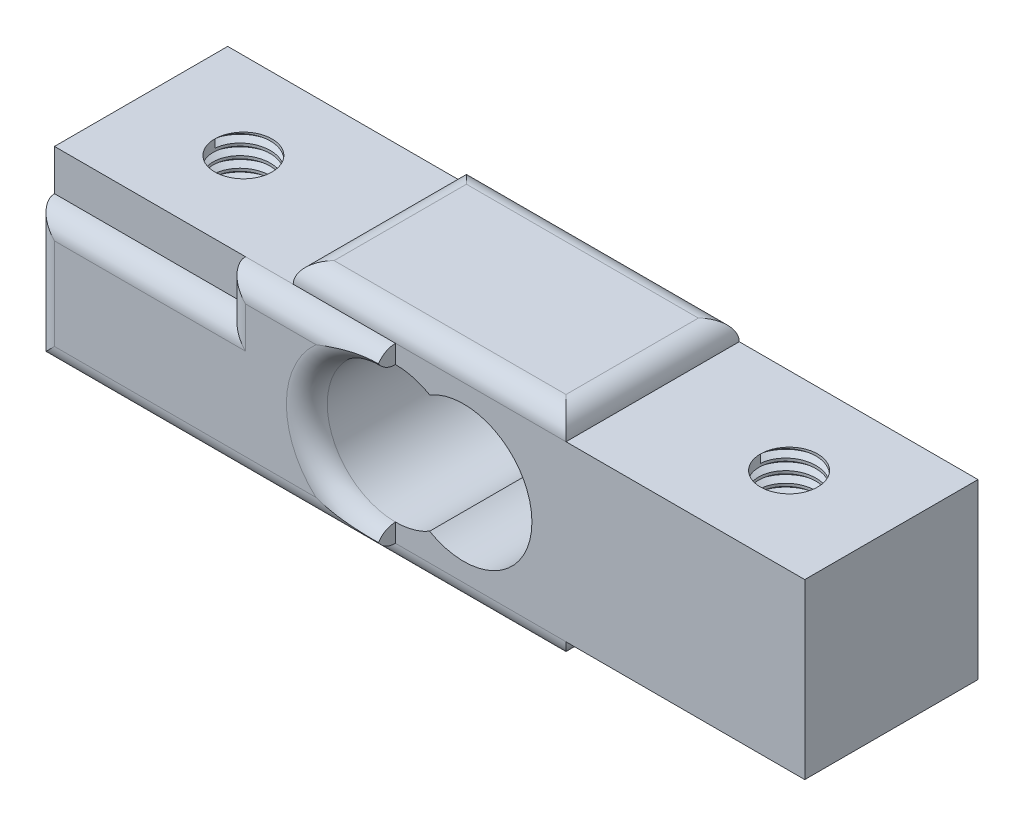
SolidWorks part; units mm, degrees
ref_plane "Front Plane" through (0, 0, 0) normal (0, 0, 1) x (1, 0, 0)
ref_plane "Top Plane" through (0, 0, 0) normal (0, 1, 0) x (1, 0, 0)
ref_plane "Right Plane" through (0, 0, 0) normal (1, 0, 0) x (0, 0, -1)
sketch "Sketch2" plane through (0, 0, 0) normal (0, 0, 1) x (1, 0, 0)
  line L1 (-27.5, -6.35) -> (27.5, -6.35)
  line L2 (-27.5, -6.35) -> (-27.5, 6.35)
  line L3 (-27.5, 6.35) -> (27.5, 6.35)
  line L4 (27.5, -6.35) -> (27.5, 6.35)
  line L5 (-27.5, -6.35) -> (27.5, 6.35) construction
  line L6 (-27.5, 6.35) -> (27.5, -6.35) construction
  point P0 (0, 0)
  dimension "D1" = 55
  dimension "D2" = 12.7
extrude "Boss-Extrude1" add sketch "Sketch2" along normal blind 12.7
sketch "Sketch3" plane through (0, 6.35, 0) normal (0, 1, 0) x (1, 0, 0)
  line L0 (-27.5, -6.35) -> (-20, -6.35) construction
  line L1 (-27.5, -12.7) -> (-27.5, 0) construction
  line L2 (27.5, -6.35) -> (20, -6.35) construction
  line L3 (27.5, -12.7) -> (27.5, 0) construction
  circle A0 centre (-20, -6.35) radius 2.5
  circle A1 centre (20, -6.35) radius 2.5
  dimension "D1" = 5
  dimension "D2" = 5
  dimension "D3" = 7.5
  dimension "D4" = 7.5
  dimension "D5" = 40
sketch "Sketch4" plane through (0, 0, 12.7) normal (0, 0, 1) x (1, 0, 0)
  line L0 (0, 0) -> (-2.5, 0) construction
  line L1 (0, 0) -> (2.5, 0) construction
  circle A0 centre (-2.5, 0) radius 5
  circle A1 centre (2.5, 0) radius 5
  dimension "D3" = 10
  dimension "D4" = 10
  dimension "D1" = 2.5
  dimension "D2" = 2.5
extrude "Cut-Extrude2" cut sketch "Sketch4" against normal blind 12.7 contours A0 A1 | A0 A1 | A1 A0 region at (0, 0, 12.7) region at (4.1051, 0, 12.7) region at (-4.1051, 0, 12.7)
sketch "Sketch5" plane through (0, 6.35, 0) normal (0, 1, 0) x (1, 0, 0)
  line L2 (-10, -6.35) -> (-10, -12.7) construction
  line L3 (27.5, -12.7) -> (-27.5, -12.7) construction
  line L4 (-10, -12.7) -> (10, -12.7) construction
  line L5 (10, -12.7) -> (10, 0) construction
  line L6 (27.5, 0) -> (-27.5, 0) construction
  line L7 (10, 0) -> (-10, 0) construction
  line L8 (-10, 0) -> (-10, -6.35) construction
  line L9 (10, -6.35) -> (27.5, -6.35) construction
  line L10 (-10, -12.7) -> (10, -12.7)
  line L11 (-10, -12.7) -> (-10, 0)
  line L12 (-10, 0) -> (10, 0)
  line L13 (10, -12.7) -> (10, 0)
  line L14 (-10, -6.35) -> (-27.5, -6.35) construction
  dimension "D1" = 20
extrude "Boss-Extrude2" add sketch "Sketch5" along normal blind 1.5
hole_wizard "Tap Drill for M5x0.8 Tap1" positions "3DSketch1" profile "Sketch8" hole size "M5x0.8" standard "ANSI Metric" end condition through all
sketch3d "3DSketch1"
  point P0 (-20, 6.35, 6.35)
  point P3 (20, 6.35, 6.35)
sketch "Sketch8" plane through (-20, 6.35, 6.35) normal (1, 0, 0) x (0, 0, 1)
  line L0 (0, 0) -> (0, 12.7)
  line L1 (0, 12.7) -> (2.1, 12.7)
  line L2 (2.1, 12.7) -> (2.1, 0)
  line L5 (2.1, 0) -> (0, 0)
  line L11 (0, -6.35) -> (0, 107.95) construction
  dimension "Thru Hole Dia." = 4.2
  dimension "Thru Hole Depth" = 12.7
fillet "Fillet1" radius 1.5 4 edges at (0, 7.85, 0) (10, 7.85, 6.35) (-10, 7.85, 6.35) (0, 7.85, 12.7)
sketch "Sketch6" plane through (0, -6.35, 0) normal (0, -1, 0) x (-1, 0, 0)
  line L0 (10, -6.35) -> (27.5, -6.35) construction
  line L1 (27.5, -12.7) -> (27.5, 0) construction
  line L2 (10, -6.35) -> (10, 0) construction
  line L3 (27.5, 0) -> (-27.5, 0) construction
  line L4 (10, 0) -> (-10, 0) construction
  line L5 (-10, 0) -> (-10, -12.7) construction
  line L6 (-10, -12.7) -> (10, -12.7) construction
  line L7 (27.5, -12.7) -> (-27.5, -12.7) construction
  line L8 (10, -12.7) -> (10, -6.35) construction
  line L10 (10, 0) -> (-10, 0)
  line L11 (10, 0) -> (10, -12.7)
  line L12 (10, -12.7) -> (-10, -12.7)
  line L13 (-10, 0) -> (-10, -12.7)
  dimension "D1" = 20
extrude "Boss-Extrude3" add sketch "Sketch6" along normal blind 1.5
fillet "Fillet2" radius 1.5 4 edges at (0, -7.85, 12.7) (10, -7.85, 6.35) (-10, -7.85, 6.35) (0, -7.85, 0)
sketch "Sketch7" plane through (0, 0, 12.7) normal (0, 0, 1) x (1, 0, 0)
  line L0 (-27.5, -6.35) -> (-27.5, 3.35) construction
  line L1 (-2.5, -6.35) -> (-2.5, -5)
  line L2 (-27.5, 6.35) -> (-27.5, -6.35) construction
  line L3 (-27.5, 3.35) -> (-13.5, 3.35) construction
  line L4 (-13.5, 3.35) -> (-13.5, 6.35) construction
  line L5 (-10, 6.35) -> (-27.5, 6.35) construction
  line L6 (-13.5, 6.35) -> (-2.5, 6.35) construction
  line L7 (10, 6.35) -> (-10, 6.35) construction
  line L8 (-27.5, -6.35) -> (-2.5, -6.35) construction
  line L9 (-10, -6.35) -> (10, -6.35) construction
  line L10 (-2.5, 6.35) -> (-13.5, 6.35)
  line L11 (-13.5, 6.35) -> (-13.5, 3.35)
  line L12 (-13.5, 3.35) -> (-27.5, 3.35)
  line L13 (-27.5, 3.35) -> (-27.5, -6.35)
  line L14 (-27.5, -6.35) -> (-2.5, -6.35)
  line L15 (-2.5, 5) -> (-2.5, 6.35)
  arc A3 (0, 4.3301) -> (0, -4.3301) centre (-2.5, 0) ccw construction
  arc A4 (-2.5, 5) -> (-2.5, -5) centre (-2.5, 0) ccw
  dimension "D1" = 9.7
  dimension "D2" = 14
extrude "Boss-Extrude4" add sketch "Sketch7" along normal blind 1.5
fillet "Fillet3" radius 1.5 6 edges at (-8, 6.35, 14.2) (-13.5, 4.85, 14.2) (-20.5, 3.35, 14.2) (-15, -6.35, 14.2) (-27.5, -1.5, 14.2) (-7.5, 0, 14.2)
thread "Thread2" pitch 0.8 method cut profile "Thread Profile2" start angle 0, offset 0, length 12.7, pitch 0.8, diameter 4.2
ref_plane "Plane2" through (17.9, 6.35, 6.35) normal (0, 0, 1) x (-1, 0, 0)
sketch "Thread Profile2" plane through (17.9, 6.35, 6.35) normal (0, 0, 1) x (-1, 0, 0)
  line L0 (0, 0) -> (0, 0.8) construction
  line L1 (0, 0) -> (0.433, 0.25)
  line L2 (0.433, 0.25) -> (0.433, 0.35)
  line L3 (0.433, 0.35) -> (0, 0.6)
  line L4 (0.433, 0.3) -> (0, 0.3) construction
  line L11 (0, 0) -> (0, 0.6)
  point P2 (0, 0)
  dimension "Pitch" = 0.8
  dimension "Profile_Angle" = 60
  dimension "Profile_Land" = 0.1
  dimension "Profile_Height" = 0.433
thread "Thread3" pitch 0.8 method cut profile "Thread Profile3" start angle 0, offset 0, length 12.7, pitch 0.8, diameter 4.2
ref_plane "Plane3" through (-22.1, 6.35, 6.35) normal (0, 0, 1) x (-1, 0, 0)
sketch "Thread Profile3" plane through (-22.1, 6.35, 6.35) normal (0, 0, 1) x (-1, 0, 0)
  line L0 (0, 0) -> (0, 0.8) construction
  line L1 (0, 0) -> (0.433, 0.25)
  line L2 (0.433, 0.25) -> (0.433, 0.35)
  line L3 (0.433, 0.35) -> (0, 0.6)
  line L4 (0.433, 0.3) -> (0, 0.3) construction
  line L11 (0, 0) -> (0, 0.6)
  point P2 (0, 0)
  dimension "Pitch" = 0.8
  dimension "Profile_Angle" = 60
  dimension "Profile_Land" = 0.1
  dimension "Profile_Height" = 0.433
sketch "Sketch17" plane through (0, 0, 0) normal (0, 0, -1) x (-1, 0, 0)
  line L0 (27.5, 6.35) -> (27.5, -6.35) construction
  line L1 (27.5, -6.35) -> (10, -6.35) construction
  line L2 (10, -6.35) -> (10, 6.35) construction
  line L3 (10, 6.35) -> (27.5, 6.35) construction
  line L4 (10, 6.35) -> (27.5, 6.35) construction
  line L5 (18.75, 6.35) -> (18.75, -6.35) construction
  line L6 (-27.5, 6.35) -> (-27.5, -6.35) construction
  line L7 (-27.5, -6.35) -> (-15, -6.35) construction
  line L8 (-10, -6.35) -> (-27.5, -6.35) construction
  line L9 (-15, -6.35) -> (-15, 6.35) construction
  line L10 (-27.5, 6.35) -> (-10, 6.35) construction
  line L11 (-15, 6.35) -> (-27.5, 6.35) construction
  line L12 (-21.25, -6.35) -> (-21.25, 6.35) construction
  point P11 (18.75, 0)
  point P16 (-21.25, 0)
